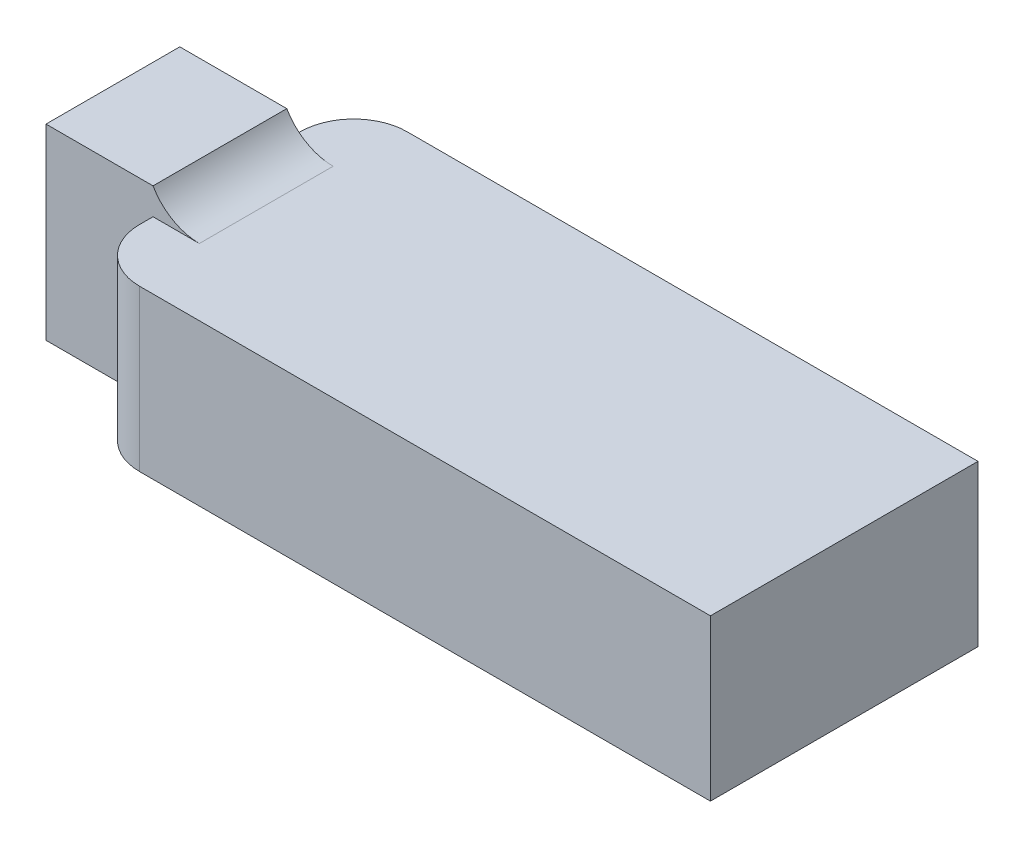
SolidWorks part; units mm, degrees
ref_plane "前视基准面" through (0, 0, 0) normal (0, 0, 1) x (1, 0, 0)
ref_plane "上视基准面" through (0, 0, 0) normal (0, 1, 0) x (1, 0, 0)
ref_plane "右视基准面" through (0, 0, 0) normal (1, 0, 0) x (0, 0, -1)
sketch "草图1" plane through (0, 0, 0) normal (0, 1, 0) x (1, 0, 0)
  line L1 (-35, 15) -> (35, 15)
  line L2 (-35, 15) -> (-35, -15)
  line L3 (-35, -15) -> (35, -15)
  line L4 (35, 15) -> (35, -15)
  line L5 (-35, 15) -> (35, -15) construction
  line L6 (-35, -15) -> (35, 15) construction
  point P0 (0, 0)
  dimension "D1" = 70
  dimension "D2" = 30
extrude "凸台-拉伸1" add sketch "草图1" along normal blind 18
fillet "圆角1" radius 6 2 edges at (-35, 9, 15) (-35, 9, -15)
sketch "草图2" plane through (-35, 0, 0) normal (-1, 0, 0) x (0, 0, 1)
  line L0 (-9, 18) -> (9, 0) construction
  line L1 (9, 18) -> (-9, 0) construction
  line L2 (0, 18) -> (0, 0) construction
  line L4 (-9, 0) -> (9, 0)
  line L5 (9, 0) -> (9, 18)
  line L6 (9, 18) -> (-9, 18)
  line L7 (-9, 18) -> (-9, 0)
  line L8 (-9, 0) -> (9, 0)
  line L9 (9, 0) -> (9, 18)
  line L10 (9, 18) -> (-9, 18)
  line L11 (-9, 18) -> (-9, 0)
  line L12 (-7.5, 0) -> (7.5, 0)
  line L13 (-7.5, 0) -> (-7.5, 21)
  line L14 (-7.5, 21) -> (7.5, 21)
  line L15 (7.5, 0) -> (7.5, 21)
  point P7 (0, 9)
  dimension "D2" = 15
  dimension "D3" = 1.5
  dimension "D4" = 21
  dimension "D1" = 0
extrude "凸台-拉伸2" add sketch "草图2" along normal blind 12 contours L10 L15 L14 L13 | L8 L15 L10 L13 region at (-35, 9, 0) region at (-35, 19.5, 0)
fillet "圆角2" radius 6 1 edges at (-35, 18, 0)
